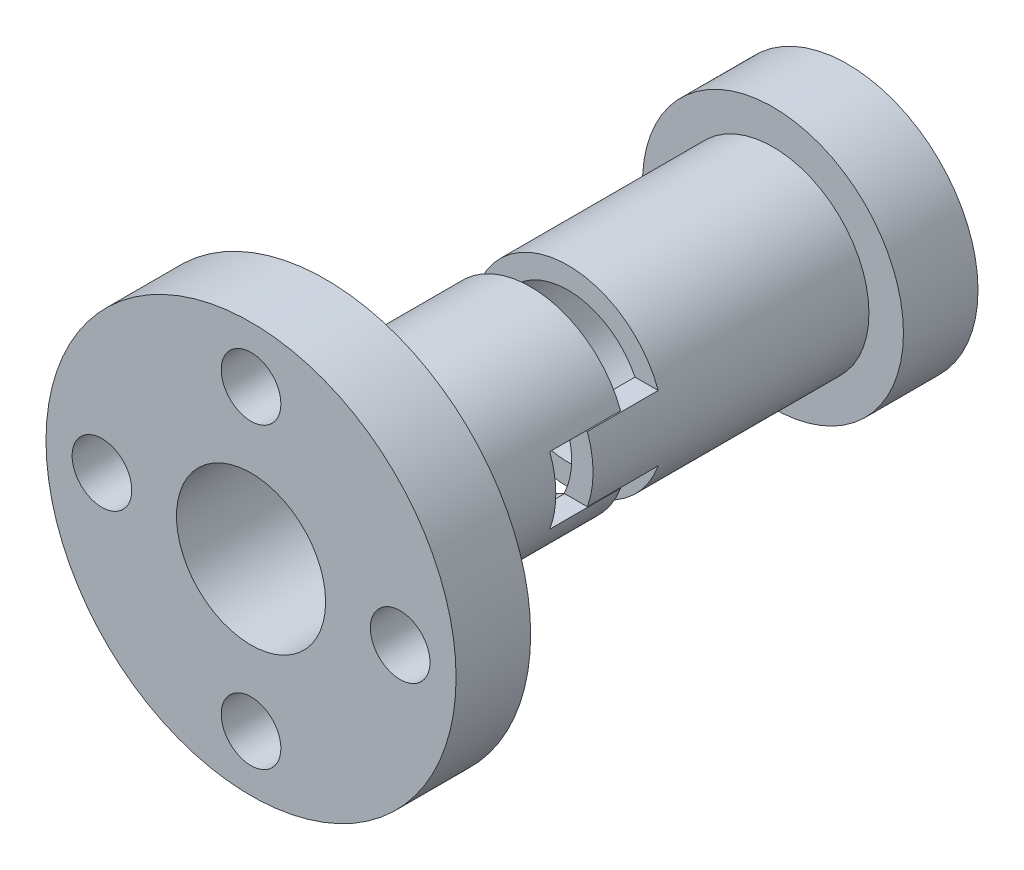
SolidWorks part; units mm, degrees
material "Bronce comercial, UNS C22000 (90-10 bronce)"
ref_plane "Front Plane" through (0, 0, 0) normal (0, 0, 1) x (1, 0, 0)
ref_plane "Top Plane" through (0, 0, 0) normal (0, 1, 0) x (1, 0, 0)
ref_plane "Right Plane" through (0, 0, 0) normal (1, 0, 0) x (0, 0, -1)
sketch "Croquis1" plane through (0, 0, 0) normal (1, 0, 0) x (0, 0, -1)
  line L0 (0, 4) -> (0, 11)
  line L1 (0, 11) -> (4, 11)
  line L2 (4, 11) -> (4, 5.15)
  line L3 (4, 5.15) -> (28, 5.15)
  line L5 (32, 4) -> (0, 4)
  line L6 (0, 0) -> (15, 0) construction
  line L7 (28, 5.15) -> (28, 7)
  line L8 (28, 7) -> (32, 7)
  line L9 (32, 7) -> (32, 4)
  dimension "D1" = 4
  dimension "D2" = 11
  dimension "D3" = 5.15
  dimension "D4" = 4
  dimension "D5" = 32
  dimension "D6" = 4
  dimension "D7" = 7
revolve "Revolución1" add sketch "Croquis1" angle 360 about L6
hole_wizard "Taladro de margen para M31" positions "Croquis2" profile "Croquis3" hole size "M3" standard "ISO"
sketch "Croquis2" plane through (0, 0, 0) normal (0, 0, 1) x (1, 0, 0)
  point P0 (8, 0)
  dimension "D1" = 8
sketch "Croquis3" plane through (8, 0, 0) normal (1, 0, 0) x (0, -1, 0)
  line L0 (0, 0) -> (0, 8.6)
  line L1 (0, 8.6) -> (1.6, 7)
  line L2 (1.6, 7) -> (1.6, 0)
  line L5 (1.6, 0) -> (0, 0)
  line L10 (0, 8.6) -> (-1.6, 7) construction
  line L11 (0, -6.35) -> (0, 107.95) construction
  dimension "Diámetro de taladro" = 3.2
  dimension "Profundidad de taladro" = 7
  dimension "Ángulo de perforador" = 90
pattern_circular "MatrizC1" count 4 over 360 about axis through (0, 0, 0) along (0, 0, -1) of "Taladro de margen para M31" reverse direction yes
sketch "Croquis4" plane through (0, 0, 0) normal (1, 0, 0) x (0, 0, -1)
  line L1 (11.2, -1.8) -> (15, -1.8)
  line L2 (11.2, -1.8) -> (11.2, 1.8)
  line L3 (11.2, 1.8) -> (15, 1.8)
  line L7 (15, 1.8) -> (15, 5.15)
  line L8 (28, 5.15) -> (4, 5.15) construction
  line L9 (15, 5.15) -> (17, 5.15)
  line L10 (17, 5.15) -> (17, 1.75)
  line L11 (17, 1.75) -> (13.2, 1.75)
  line L12 (13.2, 1.75) -> (13.2, -1.75)
  line L13 (13.2, -1.75) -> (17, -1.75)
  line L14 (17, -1.75) -> (17, -5.15)
  line L15 (17, -5.15) -> (15, -5.15)
  line L16 (15, -5.15) -> (15, -1.8)
  point P0 (11.2, 0)
  point P5 (13.2, 0)
  dimension "D3" = 10.3
  dimension "D1" = 3.6
  dimension "D2" = 3.8
  dimension "D4" = 2
  dimension "D5" = 3.5
  dimension "D6" = 15
  dimension "D7" = 2
extrude "Cortar-Extruir1" cut sketch "Croquis4" against normal through all and the other way through all
